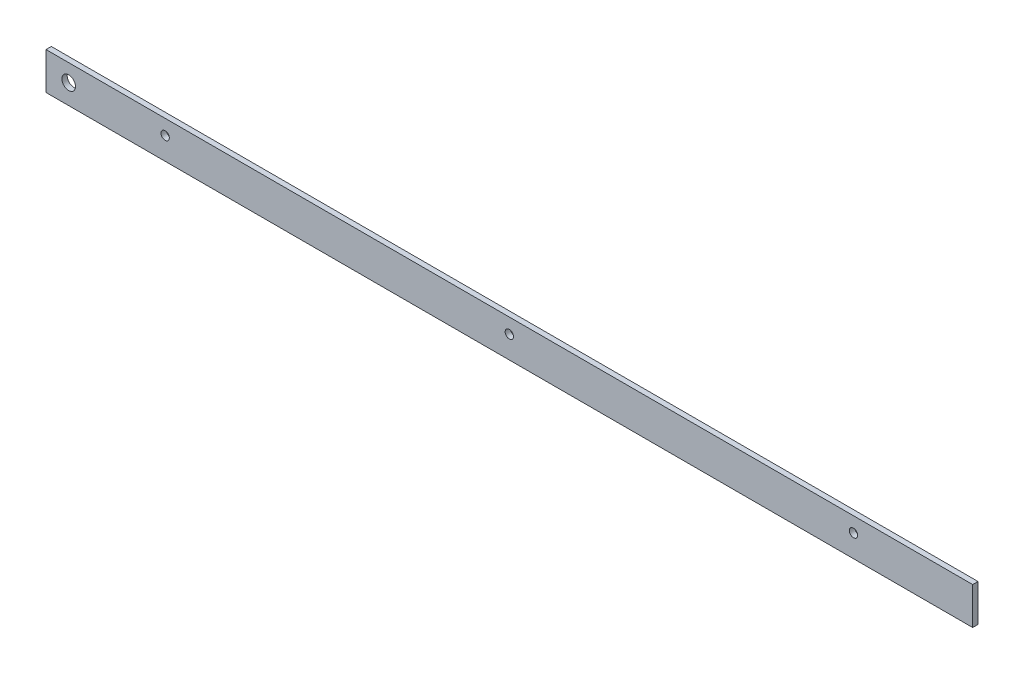
SolidWorks part; units mm, degrees
ref_plane "Front Plane" through (0, 0, 0) normal (0, 0, 1) x (1, 0, 0)
ref_plane "Top Plane" through (0, 0, 0) normal (0, 1, 0) x (1, 0, 0)
ref_plane "Right Plane" through (0, 0, 0) normal (1, 0, 0) x (0, 0, -1)
sketch "Sketch1" plane through (0, 0, 0) normal (0, 0, 1) x (1, 0, 0)
  line L0 (515.86, 17.392) -> (0, 17.392) construction
  line L5 (0, 20.567) -> (553.1, 20.567) construction
  line L6 (0, -4.833) -> (0, 45.967) construction
  line L9 (0, -4.833) -> (553.1, -4.833)
  line L10 (553.1, 17.392) -> (553.1, -4.833)
  line L12 (420.6941, 17.392) -> (0, 17.392)
  line L13 (0, -4.833) -> (0, 17.392)
  line L14 (420.6941, 17.392) -> (553.1, 17.392)
  line L19 (0, 20.567) -> (457.2, 20.567) construction
  circle A0 centre (71.12, 8.5095) radius 2.4892 construction
  circle A1 centre (13.54, 34.107) radius 13.54 construction
  circle A2 centre (13.54, 34.107) radius 4.0635 construction
  circle A3 centre (276.55, 8.5095) radius 2.4892 construction
  circle A4 centre (481.98, 8.5095) radius 2.4892 construction
  circle A5 centre (13.54, 34.107) radius 12.27 construction
  circle A6 centre (71.12, 8.5095) radius 2.4892
  circle A7 centre (276.55, 8.5095) radius 2.4892
  circle A8 centre (481.98, 8.5095) radius 2.4892
  circle A9 centre (13.54, 7.027) radius 4.0635
  point P3 (553.1, -4.833)
  point P5 (504.7465, 17.392)
  point P12 (0, 0)
  point P15 (0, 0)
  dimension "D1" = 8.127
extrude "Boss-Extrude1" add sketch "Sketch1" along normal blind 3.175 contours L14 L12 L13 L9 L10 A8 A7 A6 region at (277.6699, 6.2656, 0)
